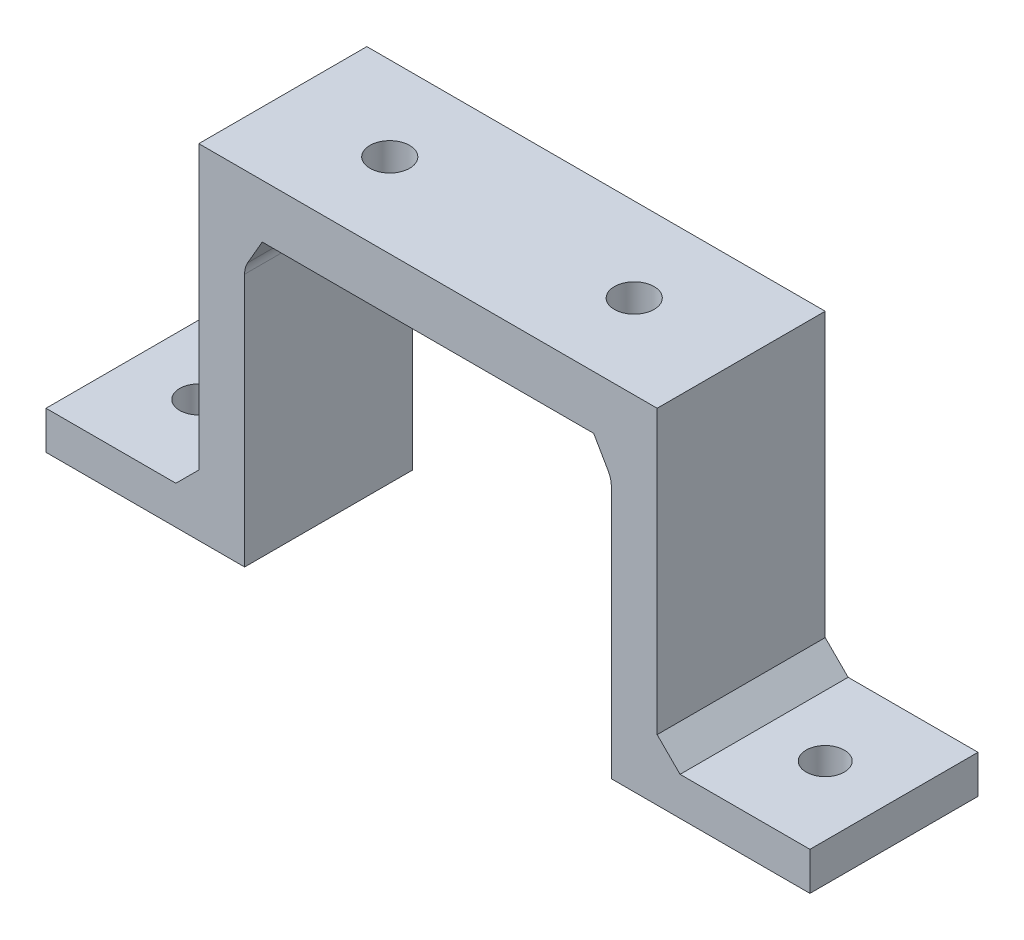
SolidWorks part; units mm, degrees
ref_plane "Front Plane" through (0, 0, 0) normal (0, 0, 1) x (1, 0, 0)
ref_plane "Top Plane" through (0, 0, 0) normal (0, 1, 0) x (1, 0, 0)
ref_plane "Right Plane" through (0, 0, 0) normal (1, 0, 0) x (0, 0, -1)
sketch "Sketch1" plane through (0, 0, 0) normal (0, 0, 1) x (1, 0, 0)
  line L0 (0, 33.7644) -> (0, -30.8661) construction
  line L1 (30, 33.7644) -> (-30, 33.7644)
  line L2 (-30, 33.7644) -> (-30, -6.2356)
  line L3 (-30, -6.2356) -> (-50, -6.2356)
  line L4 (-50, -6.2356) -> (-50, -11.2356)
  line L5 (-50, -11.2356) -> (-24, -11.2356)
  line L6 (-24, -11.2356) -> (-24, 26.7644)
  line L7 (-24, 26.7644) -> (24, 26.7644)
  line L8 (24, -11.2356) -> (24, 26.7644)
  line L9 (50, -11.2356) -> (24, -11.2356)
  line L10 (50, -6.2356) -> (50, -11.2356)
  line L11 (30, -6.2356) -> (50, -6.2356)
  line L12 (30, 33.7644) -> (30, -6.2356)
  point P11 (0, 26.7644)
  dimension "D1" = 45
  dimension "D2" = 5
  dimension "D3" = 6
  dimension "D4" = 30
  dimension "D5" = 20
  dimension "D6" = 7
extrude "Boss-Extrude1" add sketch "Sketch1" along normal blind 22
sketch "Sketch2" plane through (0, 33.7644, 0) normal (0, 1, 0) x (1, 0, 0)
  line L0 (0, 0) -> (0, -22) construction
  line L1 (30, -22) -> (-30, -22) construction
  line L2 (30, 0) -> (-30, 0) construction
  circle A0 centre (-16, -11) radius 2.6
  circle A1 centre (16, -11) radius 2.6
  dimension "D1" = 5.2
  dimension "D2" = 16
  dimension "D3" = 11
extrude "Cut-Extrude1" cut sketch "Sketch2" against normal blind 20
sketch "Sketch3" plane through (0, -6.2356, 0) normal (0, 1, 0) x (1, 0, 0)
  line L0 (-30, -22) -> (-30, 0) construction
  line L2 (-30, 0) -> (-50, 0) construction
  circle A0 centre (-41, -11) radius 2.5
  point P8 (0, 0)
  dimension "D1" = 5
  dimension "D2" = 11
  dimension "D3" = 11
extrude "Cut-Extrude2" cut sketch "Sketch3" against normal blind 20
mirror "Mirror1" about plane through (0, 0, 0) normal (1, 0, 0) of "Cut-Extrude2"
chamfer "Chamfer1" distance 4 angle 30 1 edges at (-24, 26.7644, 11) first distance on face at (-24, 7.7644, 11)
chamfer "Chamfer2" distance 4 angle 30 1 edges at (24, 26.7644, 11) first distance on face at (24, 7.7644, 11)
fillet "Fillet2" radius 3 2 edges at (24, 22.7644, 11) (-24, 22.7644, 11)
chamfer "Chamfer3" distance 3 angle 45 2 edges at (-30, -6.2356, 11) (30, -6.2356, 11)
